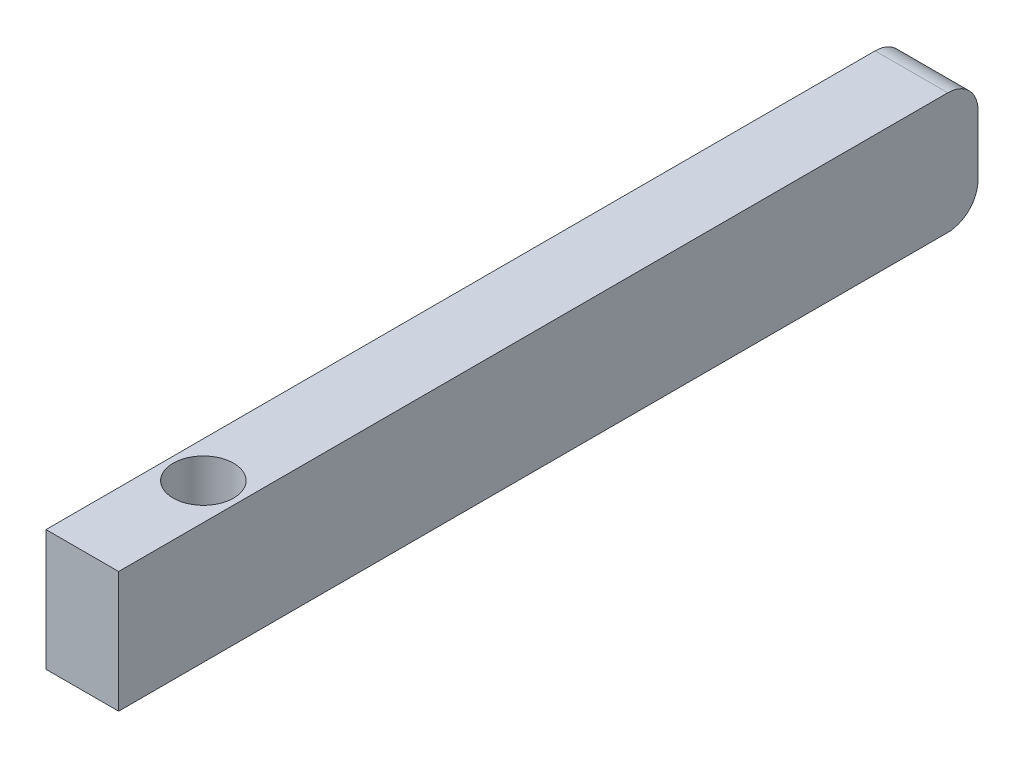
SolidWorks part; units mm, degrees
ref_plane "前视基准面" through (0, 0, 0) normal (0, 0, 1) x (1, 0, 0)
ref_plane "上视基准面" through (0, 0, 0) normal (0, 1, 0) x (1, 0, 0)
ref_plane "右视基准面" through (0, 0, 0) normal (1, 0, 0) x (0, 0, -1)
other "Configuration Table"
sketch "草图1" plane through (0, 0, 0) normal (0, 1, 0) x (1, 0, 0)
  line L49 (-0.6, -2) -> (0.6, -2)
  line L50 (-0.6, -2) -> (-0.6, 5)
  line L51 (-0.6, 5) -> (0.6, 5)
  line L52 (0.6, -2) -> (0.6, 5)
  line L53 (-0.6, 5) -> (0.6, 5)
  line L54 (-0.6, 5) -> (-0.6, 12.2)
  line L55 (-0.6, 12.2) -> (0.6, 12.2)
  line L56 (0.6, 5) -> (0.6, 12.2)
  circle A1 centre (0, 0) radius 0.5
  point P7 (0, -2)
  dimension "D12" = 1
  dimension "D2" = 7.2
  dimension "D3" = 5
  dimension "D4" = 1.2
  dimension "D5" = 2
extrude "凸台-拉伸1" add sketch "草图1" along normal blind 2 contours L51 L56 L55 L54 | L49 L52 L51 L50 A1 region at (0, 0, -1.6547) region at (0, 0, -8.6)
fillet "圆角1" radius 0.5 2 edges at (0, 2, -12.2) (0, 0, -12.2)
